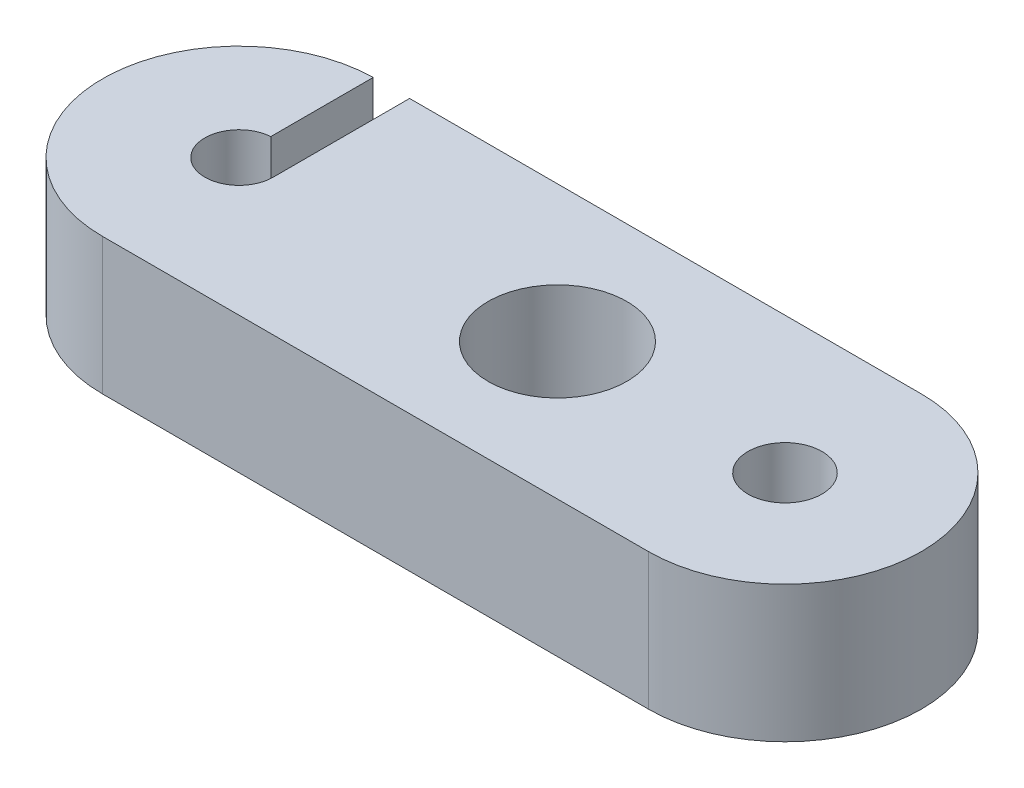
SolidWorks part; units mm, degrees
ref_plane "Front Plane" through (0, 0, 0) normal (0, 0, 1) x (1, 0, 0)
ref_plane "Top Plane" through (0, 0, 0) normal (0, 1, 0) x (1, 0, 0)
ref_plane "Right Plane" through (0, 0, 0) normal (1, 0, 0) x (0, 0, -1)
sketch "Sketch1" plane through (0, 0, 0) normal (0, 1, 0) x (1, 0, 0)
  line L0 (-3, 0) -> (3, 0) construction
  line L1 (-3, 1.5) -> (3, 1.5)
  line L2 (-3, -1.5) -> (3, -1.5)
  arc A0 (-3, 1.5) -> (-3, -1.5) centre (-3, 0) ccw
  arc A1 (3, -1.5) -> (3, 1.5) centre (3, 0) ccw
  circle A2 centre (0.5, 0) radius 0.762
  circle A3 centre (3, 0) radius 0.4064
  circle A4 centre (-3, 0) radius 0.375
  point P2 (0, 0)
  dimension "D3" = 0.8128
  dimension "D5" = 1.524
  dimension "D6" = 0.75
  dimension "D2" = 3
  dimension "D4" = 2.5
  dimension "D1" = 3.5
extrude "Boss-Extrude1" add sketch "Sketch1" along normal blind 1.5
sketch "Sketch2" plane through (0, 0, 0) normal (0, -1, 0) x (1, 0, 0)
  line L0 (-3.375, 0) -> (-2.625, 0) construction
  line L1 (-3, 0) -> (-3, -1.5) construction
  line L2 (-2.625, 0) -> (-3.025, 0)
  line L3 (-2.625, 0) -> (-2.625, -2.5)
  line L4 (-3.025, 0) -> (-3.025, -2.5)
  line L5 (-2.625, -2.5) -> (-3.025, -2.5)
  line L6 (3, -1.5) -> (-3, -1.5) construction
  circle A0 centre (-3, 0) radius 0.375 construction
  point P8 (-2.7111, 0)
  dimension "D1" = 0.4
  dimension "D2" = 1
extrude "Cut-Extrude1" cut sketch "Sketch2" against normal through all contours L3 L5 L4 L2
equation "\"StabilizerRodeHole\"=0.8128"
equation "\"D3@Sketch1\"=\"StabilizerRodeHole\""
